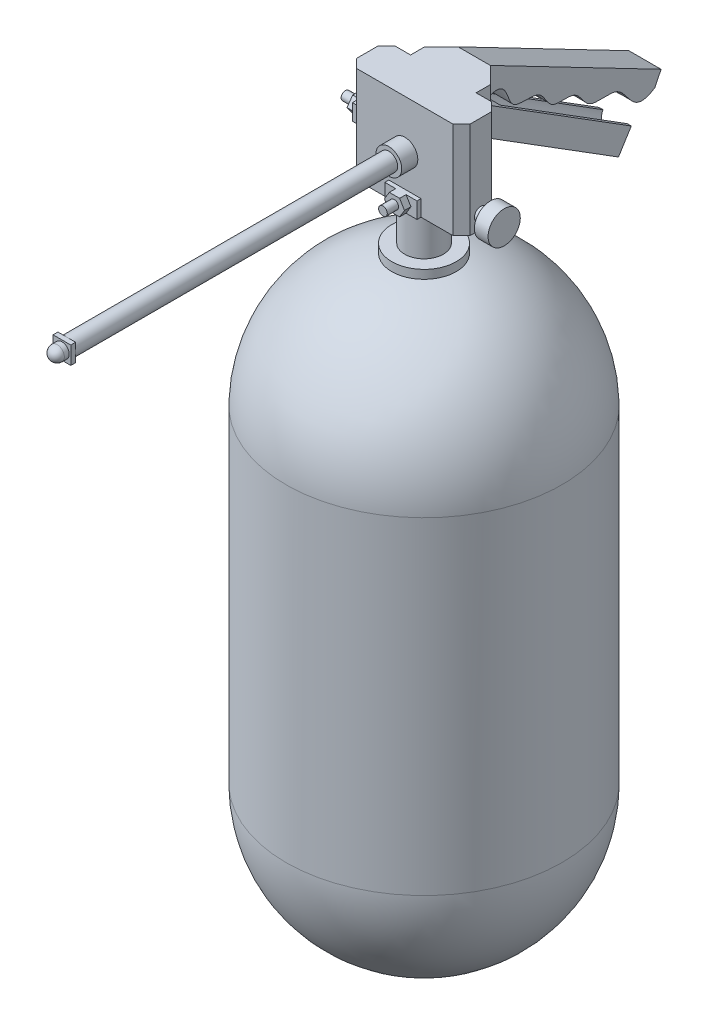
SolidWorks part; units mm, degrees
ref_plane "Front Plane" through (0, 0, 0) normal (0, 0, 1) x (1, 0, 0)
ref_plane "Top Plane" through (0, 0, 0) normal (0, 1, 0) x (1, 0, 0)
ref_plane "Right Plane" through (0, 0, 0) normal (1, 0, 0) x (0, 0, -1)
sketch "Sketch1" plane through (0, 0, 0) normal (0, 1, 0) x (1, 0, 0)
  circle A0 centre (0, 0) radius 85.725
extrude "Boss-Extrude1" add sketch "Sketch1" along normal blind 203.2
sketch3d "3DSketch5"
  line L1 (0, 313.8574, 0) -> (0, -39.2248, 0) construction
  line L2 (0, 201.578, 0) -> (-85.725, 203.2, 0)
  arc A0 (0, 287.3184, 0) -> (-85.725, 203.2, 0) centre (0, 201.578, 0) ccw
  circle A2 centre (0, 203.2, 0) radius 85.725 construction
  point P3 (0, 201.578, 85.7403)
  point P7 (0, 288.925, 0)
sketch "Sketch28" plane through (0, 0, 0) normal (0, 0, 1) x (1, 0, 0)
  line L0 (0, 287.3184) -> (0, 201.578)
  line L1 (-85.725, 203.2) -> (0, 201.578)
  arc A0 (0, 287.3184) -> (-85.725, 203.2) centre (0, 201.578) ccw
revolve "Revolve1" add sketch "Sketch28" angle 360 about L1
sketch "Sketch29" plane through (0, 0, 0) normal (0, 0, 1) x (1, 0, 0)
  line L0 (0, 0) -> (0, -85.725)
  line L1 (85.725, 0) -> (0, 0)
  arc A0 (0, -85.725) -> (85.725, 0) centre (0, 0) ccw
revolve "Revolve2" add sketch "Sketch29" angle 360 about L1
ref_plane "Plane1" through (0, 287.3184, 0) normal (0, 1, 0) x (1, 0, 0)
sketch "Sketch31" plane through (0, 287.3184, 0) normal (0, 1, 0) x (1, 0, 0)
  circle A0 centre (0, 0) radius 20
extrude "Boss-Extrude2" add sketch "Sketch31" along normal blind 3 and the other way blind 3
sketch "Sketch32" plane through (0, 290.3184, 0) normal (0, 1, 0) x (1, 0, 0)
  circle A0 centre (0, 0) radius 12
extrude "Boss-Extrude3" add sketch "Sketch32" along normal blind 25 contours A0
sketch "Sketch33" plane through (0, 315.3184, 0) normal (0, 1, 0) x (1, 0, 0)
  line L0 (30, 12) -> (-30, 12)
  line L1 (30, 12) -> (35.2894, 6.7106)
  line L2 (0, 27.9717) -> (0, -27.4313) construction
  line L3 (56.5554, 0) -> (-34.5278, 0) construction
  line L4 (0, 0) -> (-85.725, 0) construction
  line L5 (35.2894, 6.7106) -> (35.2894, -6.7106)
  line L6 (30, -12) -> (35.2894, -6.7106)
  line L7 (30, -12) -> (-30, -12)
  line L8 (-30, -12) -> (-35.2894, -6.7106)
  line L9 (-30, 12) -> (-35.2894, 6.7106)
  line L10 (-35.2894, 6.7106) -> (-35.2894, -6.7106)
  circle A0 centre (0, 0) radius 12 construction
  circle A1 centre (0, 0) radius 12 construction
  point P16 (35.2894, 0)
  point P20 (0, -12)
  point P22 (0, 12)
extrude "Boss-Extrude6" add sketch "Sketch33" along normal blind 60
sketch "Sketch34" plane through (35.2894, 0, 0) normal (1, 0, 0) x (0, 0, -1)
  circle A0 centre (0, 323.7255) radius 4
extrude "Boss-Extrude7" add sketch "Sketch34" along normal blind 6
sketch "Sketch35" plane through (41.2894, 0, 0) normal (1, 0, 0) x (0, 0, -1)
  circle A0 centre (0, 323.7255) radius 10
extrude "Boss-Extrude8" add sketch "Sketch35" along normal blind 8.5
sketch "Sketch36" plane through (0, 0, 12) normal (0, 0, 1) x (1, 0, 0)
  line L0 (10.144, 315.3184) -> (10.144, 325.3184)
  line L1 (0, 315.3184) -> (30, 315.3184) construction
  line L2 (10.144, 315.3184) -> (-9.856, 315.3184)
  line L4 (-30, 315.3184) -> (0, 315.3184) construction
  line L5 (10.144, 325.3184) -> (-9.856, 325.3184)
  line L6 (-9.856, 325.3184) -> (-9.856, 315.3184)
extrude "Boss-Extrude9" add sketch "Sketch36" along normal blind 2.5
sketch "Sketch37" plane through (0, 0, 14.5) normal (0, 0, 1) x (1, 0, 0)
  line L0 (0.144, 325.3184) -> (3.344, 325.3184)
  line L2 (0.144, 325.3184) -> (-3.056, 325.3184)
  line L3 (-3.056, 325.3184) -> (-6.0984, 320.3184)
  line L4 (-6.0984, 320.3184) -> (-3.056, 315.3184)
  line L5 (10.144, 325.3184) -> (-9.856, 325.3184) construction
  line L6 (10.144, 325.3184) -> (-9.856, 325.3184) construction
  line L7 (-12, 315.3184) -> (12, 315.3184) construction
  line L8 (-3.056, 315.3184) -> (3.344, 315.3184)
  line L9 (-9.856, 315.3184) -> (10.144, 315.3184) construction
  line L11 (3.344, 325.3184) -> (6.3864, 320.3184)
  line L13 (6.3864, 320.3184) -> (3.344, 315.3184)
extrude "Boss-Extrude10" add sketch "Sketch37" along normal blind 4
sketch "Sketch38" plane through (0, 0, 18.5) normal (0, 0, 1) x (1, 0, 0)
  circle A0 centre (0, 320.3184) radius 2.7
extrude "Boss-Extrude11" add sketch "Sketch38" along normal blind 7
sketch "Sketch39" plane through (-35.2894, 0, 0) normal (-1, 0, 0) x (0, 0, 1)
  line L0 (6.7106, 350.3184) -> (-6.7106, 350.3184)
  line L1 (6.7106, 375.3184) -> (6.7106, 315.3184) construction
  line L2 (6.7106, 340.3184) -> (6.7106, 350.3184)
  line L3 (-6.7106, 375.3184) -> (-6.7106, 315.3184) construction
  line L4 (-6.7106, 350.3184) -> (-6.7106, 340.3184)
  line L5 (-6.7106, 340.3184) -> (6.7106, 340.3184)
extrude "Boss-Extrude12" add sketch "Sketch39" along normal blind 2.5
sketch "Sketch40" plane through (-37.7894, 0, 0) normal (-1, 0, 0) x (0, 0, 1)
  line L1 (2.5, 350.3184) -> (6.0389, 345.3184)
  line L2 (6.7106, 350.3184) -> (-6.7106, 350.3184) construction
  line L4 (-2.5, 350.3184) -> (2.5, 350.3184)
  line L5 (6.0389, 345.3184) -> (2.5, 340.3184)
  line L6 (-6.7106, 340.3184) -> (6.7106, 340.3184) construction
  line L8 (2.5, 340.3184) -> (-2.5, 340.3184)
  line L9 (-6.7106, 340.3184) -> (6.7106, 340.3184) construction
  line L10 (0, 350.3184) -> (0, 340.0754) construction
  line L11 (-6.0389, 345.3184) -> (-2.5, 340.3184)
  line L12 (-2.5, 350.3184) -> (-6.0389, 345.3184)
extrude "Boss-Extrude13" add sketch "Sketch40" along normal blind 4
sketch "Sketch41" plane through (-41.7894, 0, 0) normal (-1, 0, 0) x (0, 0, 1)
  circle A0 centre (0, 345.3184) radius 2.7
extrude "Boss-Extrude14" add sketch "Sketch41" along normal blind 7
sketch "Sketch42" plane through (0, 0, 12) normal (0, 0, 1) x (1, 0, 0)
  circle A0 centre (0.144, 345.3184) radius 8
extrude "Boss-Extrude15" add sketch "Sketch42" along normal blind 10
sketch "Sketch43" plane through (0, 0, 22) normal (0, 0, 1) x (1, 0, 0)
  circle A0 centre (0.144, 345.3184) radius 5.5
extrude "Boss-Extrude16" add sketch "Sketch43" along normal blind 200
sketch "Sketch44" plane through (0, 0, 222) normal (0, 0, 1) x (1, 0, 0)
  line L4 (5.644, 339.8184) -> (-5.356, 339.8184)
  line L5 (-5.356, 339.8184) -> (-5.356, 350.8184)
  line L6 (-5.356, 350.8184) -> (5.644, 350.8184)
  line L7 (5.644, 350.8184) -> (5.644, 339.8184)
extrude "Boss-Extrude17" add sketch "Sketch44" along normal blind 3
sketch "Sketch45" plane through (0, 0, 225) normal (0, 0, 1) x (1, 0, 0)
  circle A0 centre (0.144, 345.3184) radius 4.5
extrude "Boss-Extrude18" add sketch "Sketch45" along normal blind 3
sketch "Sketch47" plane through (0, 0, 228) normal (0, 0, 1) x (1, 0, 0)
  line L0 (0.144, 349.8184) -> (0.144, 340.8184) construction
  circle A0 centre (0.144, 345.3184) radius 4.5 construction
revolve "Revolve3" add sketch "Sketch47" angle 180 about L0 region at (2.0538, 345.3184, 228)
sketch "Sketch48" plane through (0, 375.3184, 0) normal (0, 1, 0) x (1, 0, 0)
  line L0 (-20.3579, -12) -> (-20.3579, 20.8202)
  line L1 (-30, -12) -> (30, -12) construction
  line L3 (0, -12) -> (0, 39.6745) construction
  line L4 (-20.3579, 20.8202) -> (-10.039, 31.1391)
  line L5 (-10.039, 31.1391) -> (10.039, 31.1391)
  line L6 (20.3579, -12) -> (20.3579, 20.8202)
  line L7 (20.3579, 20.8202) -> (10.039, 31.1391)
  line L8 (20.3579, -12) -> (-20.3579, -12)
  point P12 (0, 31.1391)
extrude "Boss-Extrude19" add sketch "Sketch48" against normal blind 16
ref_plane "Plane3" through (10.039, 0, 0) normal (-1, 0, 0) x (0, 0, 1)
sketch "Sketch52" plane through (10.039, 0, 0) normal (-1, 0, 0) x (0, 0, 1)
  line L0 (-31.1391, 375.3184) -> (-137.1985, 320.2163)
  line L1 (-137.1985, 320.2163) -> (-133.3303, 312.2903)
  line L2 (-31.1391, 375.3184) -> (-31.1391, 359.3184)
  spline S0 degree 3 poles (-31.1391, 359.3184) (-42.3798, 363.1584) (-39.5917, 340.8187) (-62.8888, 349.0991) (-67.9269, 331.0532) (-84.9807, 337.1463) (-91.5296, 319.1055) (-116.3524, 328.6844) (-119.1165, 302.8083) (-133.3303, 312.2903) knots 0 0 0 0 0.166178 0.30482 0.403837 0.523806 0.628724 0.776597 1 1 1 1
extrude "Boss-Extrude20" add sketch "Sketch52" along normal blind 20
sketch "Sketch53" plane through (10.039, 0, 0) normal (-1, 0, 0) x (0, 0, 1)
  line L0 (-25.9796, 359.3184) -> (-25.9796, 339.3184)
  line L1 (-20.8202, 359.3184) -> (-31.1391, 359.3184) construction
  line L2 (-25.9796, 339.3184) -> (-110.7377, 286.2518)
  line L3 (-110.7377, 286.2518) -> (-118.6977, 298.9655)
  line L4 (-118.6977, 298.9655) -> (-31.1391, 353.7855)
  line L5 (-31.1391, 353.7855) -> (-31.1391, 359.3184)
  line L6 (-31.1391, 359.3184) -> (-25.9796, 359.3184)
extrude "Boss-Extrude21" add sketch "Sketch53" along normal blind 20
sketch "Sketch55" plane through (0, 30.8024, 49.1977) normal (0, -0.5307, -0.8476) x (-1, 0, 0)
  line L3 (7.5, 316.3863) -> (-7.5, 316.3863)
  arc A1 (-7.5, 316.3863) -> (7.5, 316.3863) centre (0, 316.3863) ccw
extrude "Cut-Extrude2" cut sketch "Sketch55" against normal blind 93
